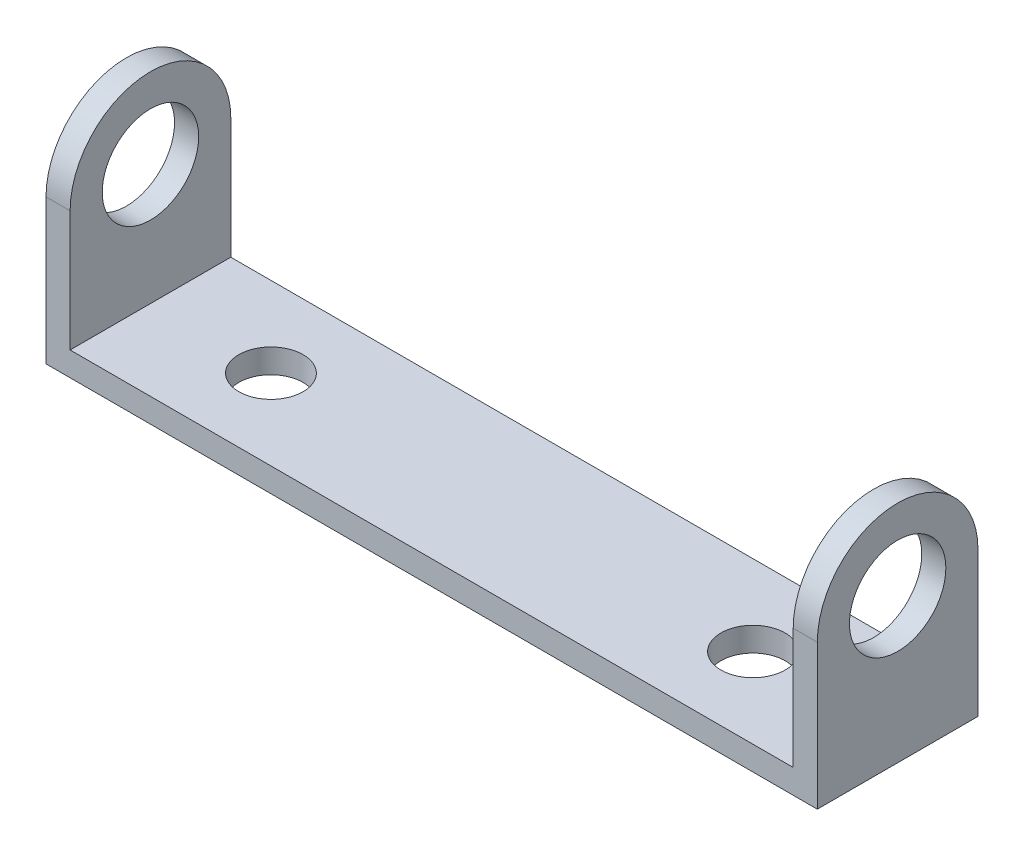
SolidWorks part; units mm, degrees
material "Plain Carbon Steel"
ref_plane "Front Plane" through (0, 0, 0) normal (0, 0, 1) x (1, 0, 0)
ref_plane "Top Plane" through (0, 0, 0) normal (0, 1, 0) x (1, 0, 0)
ref_plane "Right Plane" through (0, 0, 0) normal (1, 0, 0) x (0, 0, -1)
sketch "Sketch1" plane through (0, 0, 0) normal (0, 0, 1) x (1, 0, 0)
  line L0 (-22.5, 7) -> (-22.5, -5.5)
  line L1 (-24, -7) -> (24, -7)
  line L2 (-24, -7) -> (-24, 7)
  line L3 (-24, 7) -> (24, 7) construction
  line L4 (24, -7) -> (24, 7)
  line L5 (-24, -7) -> (24, 7) construction
  line L6 (-24, 7) -> (24, -7) construction
  line L7 (-22.5, -5.5) -> (22.5, -5.5)
  line L8 (22.5, -5.5) -> (22.5, 7)
  line L9 (24, 7) -> (22.5, 7)
  line L10 (-22.5, 7) -> (-24, 7)
  dimension "D1" = 48
  dimension "D2" = 14
  dimension "D3" = 1.5
  dimension "D4" = 1.5
  dimension "D5" = 1.5
extrude "Boss-Extrude1" add sketch "Sketch1" along normal blind 10
sketch "Sketch2" plane through (24, 0, 0) normal (1, 0, 0) x (0, 0, -1)
  line L0 (0, -7) -> (0, 7) construction
  line L1 (-10, -7) -> (-10, 7) construction
  line L2 (-10, 7) -> (0, 7) construction
  line L3 (-10, 2) -> (0, 2) construction
  line L4 (-10, 2) -> (-10, 7)
  line L5 (-10, 7) -> (0, 7)
  line L6 (0, 7) -> (0, 2)
  arc A0 (0, 2) -> (-10, 2) centre (-5, 2) ccw
  circle A1 centre (-5, 2) radius 3
  line M2 (0, -7) -> (0, 7)
  line M3 (0, 7) -> (-10, 7)
  line M4 (-10, 7) -> (-10, -7)
  dimension "D1" = 6
extrude "Cut-Extrude1" cut sketch "Sketch2" against normal up to surface (48 mm away) contours A0 L5 M4 | A0 M2 M3 | A1 L3 | L3 A1 region at (24, 0.7268, 5) region at (24, 3.2732, 5) region at (24, 5.8832, 1.1168) region at (24, 5.8832, 8.8832) up to face at (-24, 0, 5)
sketch "Sketch3" plane through (0, -5.5, 0) normal (0, 1, 0) x (1, 0, 0)
  line L0 (-22.5, 0) -> (22.5, -10) construction
  line L1 (22.5, 0) -> (-22.5, 0) construction
  line L2 (-22.5, -10) -> (-22.5, 0) construction
  line L3 (22.5, -10) -> (-22.5, -10) construction
  line L4 (0, -5) -> (22.5, -5) construction
  line L5 (22.5, -10) -> (22.5, 0) construction
  line L6 (0, -5) -> (-22.5, -5) construction
  circle A0 centre (15, -5) radius 2
  circle A1 centre (-15, -5) radius 2
  dimension "D1" = 4
  dimension "D2" = 4
  dimension "D3" = 15
  dimension "D4" = 15
extrude "Cut-Extrude2" cut sketch "Sketch3" against normal blind 10
